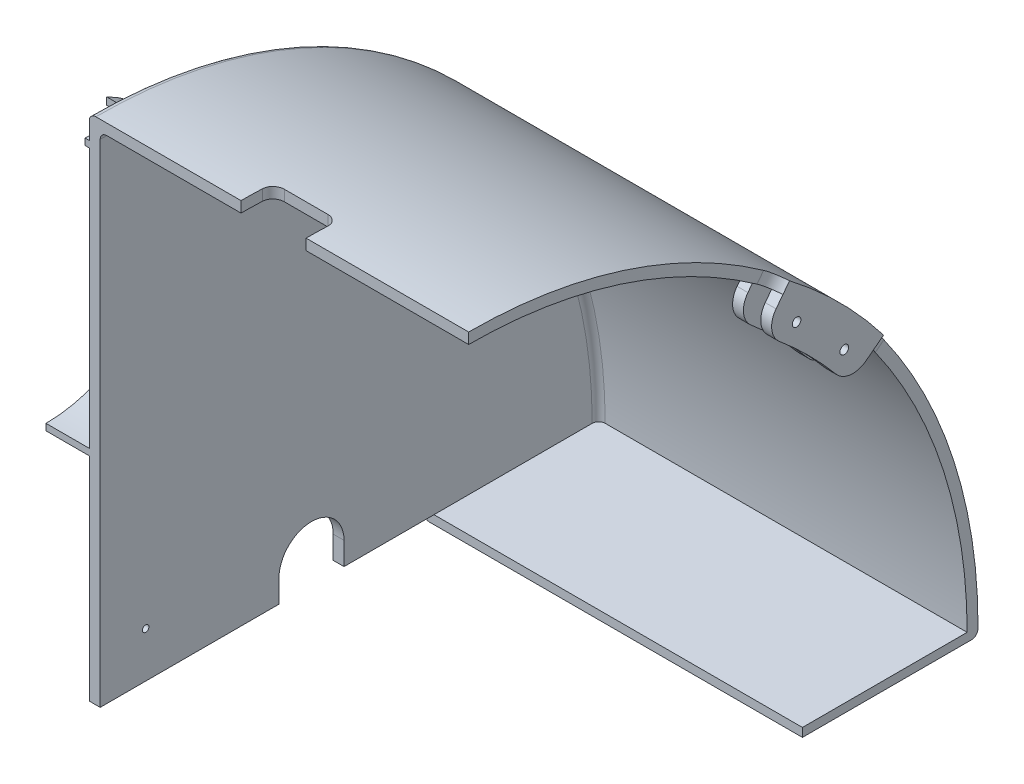
SolidWorks part; units mm, degrees
ref_plane "前视基准面" through (0, 0, 0) normal (0, 0, 1) x (1, 0, 0)
ref_plane "上视基准面" through (0, 0, 0) normal (0, 1, 0) x (1, 0, 0)
ref_plane "右视基准面" through (0, 0, 0) normal (1, 0, 0) x (0, 0, -1)
sketch "草图1" plane through (0, 0, 0) normal (1, 0, 0) x (0, 0, -1)
  circle A0 centre (0, 0) radius 235
  dimension "D1" = 470
extrude "凸台-拉伸1" add sketch "草图1" along normal blind 5
sketch "草图2" plane through (5, 0, 0) normal (1, 0, 0) x (0, 0, -1)
  circle A0 centre (0, 0) radius 230
  circle A1 centre (0, 0) radius 235
  circle A2 centre (0, 0) radius 235
  dimension "D1" = 0
  dimension "D2" = 5
extrude "凸台-拉伸2" add sketch "草图2" along normal blind 170
sketch "草图3" plane through (0, 0, 0) normal (-1, 0, 0) x (0, 0, 1)
  line L0 (0, 0) -> (0, 250)
  line L1 (0, 250) -> (330.8874, 250)
  line L2 (330.8874, 250) -> (330.8874, -253.4327)
  line L3 (330.8874, -253.4327) -> (-250, -253.4327)
  line L4 (-250, -253.4327) -> (-250, 0)
  line L5 (-250, 0) -> (0, 0)
  dimension "D1" = 250
  dimension "D2" = 250
extrude "切除-拉伸1" cut sketch "草图3" against normal through all
ref_plane "基准面1" through (167, 0, 0) normal (1, 0, 0) x (0, 0, -1)
sketch "草图4" plane through (167, 0, 0) normal (1, 0, 0) x (0, 0, -1)
  line L0 (0, 0) -> (35355.3391, 35355.3391) construction
  line L1 (230, 0) -> (0, 0) construction
  line L2 (170.571, 130.8837) -> (182.4713, 140.0151)
  line L3 (130.8837, 170.571) -> (140.0151, 182.4713)
  arc A0 (230, 0) -> (0, 230) centre (0, 0) ccw construction
  arc A1 (182.4713, 140.0151) -> (140.0151, 182.4713) centre (0, 0) ccw
  arc A2 (170.571, 130.8837) -> (130.8837, 170.571) centre (0, 0) ccw
  arc A4 (230, 0) -> (0, 230) centre (0, 0) ccw construction
  arc A5 (215, 0) -> (0, 215) centre (0, 0) ccw construction
  dimension "D2" = 45
  dimension "D3" = 7.5
  dimension "D1" = 15
extrude "凸台-拉伸3" add sketch "草图4" against normal blind 5
ref_plane "基准面2" through (59, 0, 0) normal (1, 0, 0) x (0, 0, -1)
sketch "草图5" plane through (59, 0, 0) normal (1, 0, 0) x (0, 0, -1)
  line L2 (170.571, 130.8837) -> (182.4713, 140.0151)
  line L3 (140.0151, 182.4713) -> (130.8837, 170.571)
  line L4 (170.571, 130.8837) -> (182.4713, 140.0151)
  line L5 (140.0151, 182.4713) -> (130.8837, 170.571)
  arc A2 (170.571, 130.8837) -> (130.8837, 170.571) centre (0, 0) ccw
  arc A3 (182.4713, 140.0151) -> (140.0151, 182.4713) centre (0, 0) ccw
  arc A4 (170.571, 130.8837) -> (130.8837, 170.571) centre (0, 0) ccw
  arc A5 (182.4713, 140.0151) -> (140.0151, 182.4713) centre (0, 0) ccw
  dimension "D1" = 0
extrude "凸台-拉伸4" add sketch "草图5" against normal blind 5
sketch "草图6" plane through (167, 0, 0) normal (1, 0, 0) x (0, 0, -1)
  line L2 (0, 0) -> (35355.3391, 35355.3391) construction
  line L3 (230, 0) -> (0, 0) construction
  line L4 (146.3012, 168.3002) -> (0, 0) construction
  line L5 (0, 0) -> (168.3002, 146.3012) construction
  circle A0 centre (146.3012, 168.3002) radius 2
  circle A1 centre (168.3002, 146.3012) radius 2
  dimension "D1" = 4
  dimension "D2" = 223
  dimension "D3" = 223
  dimension "D4" = 45
  dimension "D5" = 4
  dimension "D6" = 4
extrude "切除-拉伸2" cut sketch "草图6" against normal blind 5
fillet "圆角1" radius 3 2 edges at (0, 166.1701, -166.1701) (5, 162.6346, -162.6346)
sketch "草图7" plane through (175, 0, 0) normal (1, 0, 0) x (0, 0, -1)
  line L2 (170.571, 130.8837) -> (182.4713, 140.0151)
  line L3 (140.0151, 182.4713) -> (130.8837, 170.571)
  line L4 (170.571, 130.8837) -> (186.438, 143.0589)
  line L5 (143.0589, 186.438) -> (130.8837, 170.571)
  arc A0 (235, 0) -> (0, 235) centre (0, 0) ccw construction
  arc A1 (186.438, 143.0589) -> (143.0589, 186.438) centre (0, 0) ccw
  arc A2 (170.571, 130.8837) -> (130.8837, 170.571) centre (0, 0) ccw
  arc A3 (182.4713, 140.0151) -> (140.0151, 182.4713) centre (0, 0) ccw
  arc A4 (170.571, 130.8837) -> (130.8837, 170.571) centre (0, 0) ccw
  dimension "D1" = 0
extrude "凸台-拉伸5" add sketch "草图7" along normal blind 5
fillet "圆角2" radius 10 2 edges at (175, 184.4547, -141.537) (175, 141.537, -184.4547)
fillet "圆角3" radius 10 4 edges at (177.5, 130.8837, -170.571) (164.5, 130.8837, -170.571) (177.5, 170.571, -130.8837) (164.5, 170.571, -130.8837)
sketch "草图8" plane through (180, 0, 0) normal (1, 0, 0) x (0, 0, -1)
  circle A0 centre (168.3002, 146.3012) radius 2 construction
  circle A1 centre (146.3012, 168.3002) radius 2 construction
  circle A2 centre (168.3002, 146.3012) radius 2
  circle A3 centre (146.3012, 168.3002) radius 2
extrude "切除-拉伸3" cut sketch "草图8" against normal blind 5
fillet "圆角4" radius 10 2 edges at (56.5, 170.571, -130.8837) (56.5, 130.8837, -170.571)
sketch "草图10" plane through (0, 0, 0) normal (0, -1, 0) x (1, 0, 0)
  line L0 (0, 0) -> (0, -232) construction
  line L2 (0, -154) -> (0, -232)
  line L3 (175, -138.3353) -> (175, -164.5854) construction
  line L4 (175, -230) -> (8, -230) construction
  line L5 (0, -154) -> (175, -154)
  line L7 (3, -235) -> (175, -235)
  line L8 (175, -154) -> (175, -235)
  arc A0 (0, -232) -> (3, -235) centre (3, -232) ccw construction
  arc A1 (0, -232) -> (3, -235) centre (3, -232) ccw
  dimension "D1" = 76
extrude "凸台-拉伸6" add sketch "草图10" along normal blind 4
fillet "圆角5" radius 3 3 edges at (89, -4, -235) (0.8787, -4, -234.1213) (0, -4, -193)
sketch "草图11" plane through (0, 0, 0) normal (-1, 0, 0) x (0, 0, 1)
  line L0 (0, 232) -> (0, 0) construction
  line L2 (0, 224) -> (0, 221)
  line L3 (0, 98) -> (0, 101)
  line L4 (0, 161) -> (50000, 161) construction
  line L5 (-44.1723, 120.3945) -> (-46.2954, 118.2714)
  line L6 (-50.7543, 129) -> (-53.2145, 127.2774)
  line L7 (-50.7543, 193) -> (-53.2145, 194.7226)
  line L8 (-44.1723, 201.6055) -> (-46.2954, 203.7286)
  arc A0 (0, 221) -> (-44.1723, 201.6055) centre (0, 161) ccw
  arc A1 (0, 224) -> (-46.2954, 203.7286) centre (0, 161) ccw
  circle A2 centre (0, 161) radius 60 construction
  circle A3 centre (0, 161) radius 63 construction
  arc A4 (-44.1723, 120.3945) -> (0, 101) centre (0, 161) ccw
  arc A5 (-46.2954, 118.2714) -> (0, 98) centre (0, 161) ccw
  arc A6 (-53.2145, 194.7226) -> (-53.2145, 127.2774) centre (0, 161) ccw
  arc A7 (-50.7543, 193) -> (-50.7543, 129) centre (0, 161) ccw
  point P22 (-51.9844, 193.8613)
  dimension "D1" = 120
  dimension "D8" = 11
  dimension "D2" = 161
  dimension "D4" = 45
  dimension "D5" = 10
  dimension "D6" = 35
  dimension "D7" = 135
  dimension "D9" = 32
  dimension "D3" = 3
extrude "凸台-拉伸7" add sketch "草图11" along normal blind 20
sketch "草图12" plane through (0, 0, 0) normal (0, 1, 0) x (1, 0, 0)
  line L1 (-24.8964, 28) -> (-2, 28)
  line L2 (-24.8964, 28) -> (-24.8964, -23.4047)
  line L3 (-24.8964, -23.4047) -> (-2, -23.4047)
  line L4 (-2, 28) -> (-2, -23.4047)
  line L5 (8, 0) -> (175, 0) construction
  dimension "D1" = 2
  dimension "D2" = 28
extrude "切除-拉伸5" cut sketch "草图12" along normal blind 120 from offset 120
sketch "草图13" plane through (0, 0, 0) normal (0, 1, 0) x (1, 0, 0)
  line L0 (3, 0) -> (175, 0) construction
  line L1 (70, 15) -> (100, 15)
  line L2 (70, 15) -> (70, -15)
  line L3 (70, -15) -> (100, -15)
  line L4 (100, 15) -> (100, -15)
  dimension "D1" = 30
  dimension "D2" = 15
  dimension "D3" = 70
extrude "切除-拉伸6" cut sketch "草图13" along normal through all
fillet "圆角6" radius 5 2 edges at (70, 232.0156, -15) (100, 232.0156, -15)
sketch "草图14" plane through (0, 0, 0) normal (-1, 0, 0) x (0, 0, 1)
  line L0 (0, 98) -> (0, 0) construction
  line L1 (-154, -4) -> (-232, -4) construction
  line L2 (-82.5, 10.5) -> (-82.5, 0)
  line L3 (0, 0) -> (-154, 0) construction
  line L4 (-82.5, 0) -> (-112.5, 0)
  line L5 (-112.5, 0) -> (-112.5, 10.5)
  arc A0 (-82.5, 10.5) -> (-112.5, 10.5) centre (-97.5, 10.5) ccw
  dimension "D1" = 97.5
  dimension "D3" = 30
  dimension "D2" = 14.5
extrude "切除-拉伸7" cut sketch "草图14" against normal blind 10
sketch "草图15" plane through (0, 0, 0) normal (-1, 0, 0) x (0, 0, 1)
  line L0 (0, 0) -> (-82.5, 0) construction
  line L1 (-21, 21) -> (27.8746, 21) construction
  line L2 (-21, 21) -> (-21, -17.8191) construction
  line L3 (-21, -17.8191) -> (27.8746, -17.8191) construction
  line L4 (27.8746, 21) -> (27.8746, -17.8191) construction
  line L5 (0, 98) -> (0, 0) construction
  circle A0 centre (-21, 21) radius 1.5
  dimension "D3" = 3
  dimension "D1" = 21
  dimension "D2" = 21
extrude "切除-拉伸8" cut sketch "草图15" against normal blind 10
chamfer "倒角1" distance 0.5 angle 45 1 edges at (0, 21, -19.5)
sketch "草图16" plane through (0, 0, 0) normal (-1, 0, 0) x (0, 0, 1)
  line L0 (0, 0) -> (-35355.3391, 35355.3391) construction
  line L1 (0, 98) -> (0, 0) construction
  line L2 (-159.099, 137.8858) -> (-137.8858, 159.099) construction
  circle A1 centre (-159.099, 137.8858) radius 2
  circle A2 centre (-137.8858, 159.099) radius 2
  dimension "D5" = 4
  dimension "D6" = 4
  dimension "D1" = 45
  dimension "D2" = 30
  dimension "D3" = 15
  dimension "D4" = 210
extrude "切除-拉伸9" cut sketch "草图16" against normal blind 10
chamfer "倒角2" distance 0.5 angle 45 2 edges at (0, 159.099, -135.8858) (0, 137.8858, -157.099)
